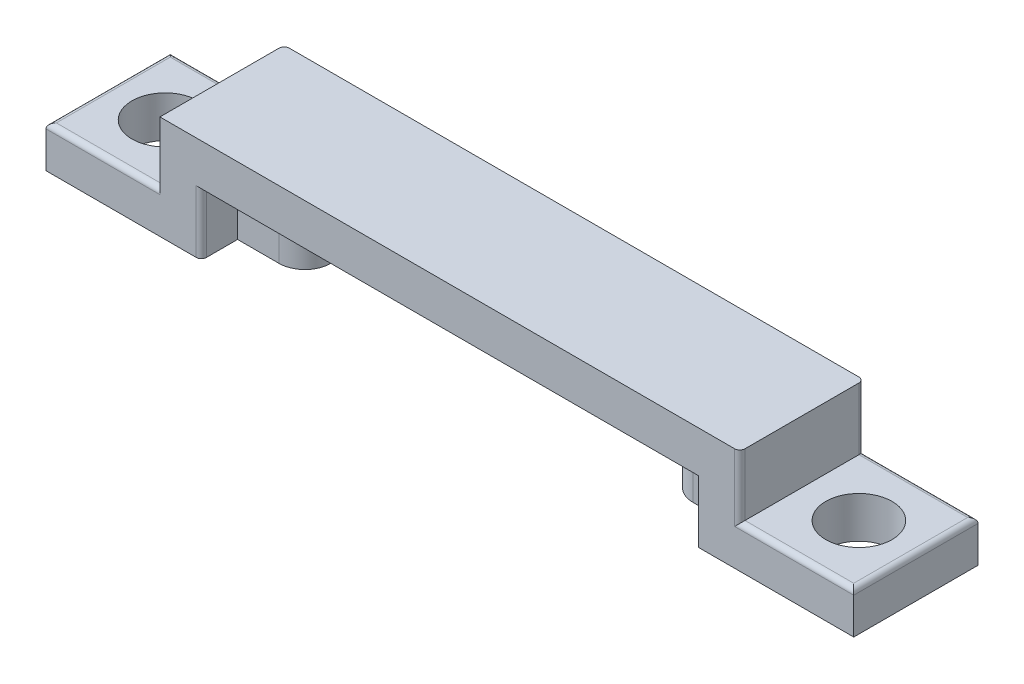
SolidWorks part; units mm, degrees
ref_plane "Ebene vorne" through (0, 0, 0) normal (0, 0, 1) x (1, 0, 0)
ref_plane "Ebene oben" through (0, 0, 0) normal (0, 1, 0) x (1, 0, 0)
ref_plane "Ebene rechts" through (0, 0, 0) normal (1, 0, 0) x (0, 0, -1)
sketch "Skizze1" plane through (0, 0, 0) normal (0, 0, 1) x (1, 0, 0)
  line L0 (0, 0) -> (7.5, 0)
  line L1 (7.5, 0) -> (7.5, 3)
  line L2 (7.5, 3) -> (31.5, 3)
  line L3 (31.5, 3) -> (31.5, 0)
  line L4 (31.5, 0) -> (39, 0)
  line L5 (39, 0) -> (39, 2)
  line L8 (33.5, 5) -> (5.5, 5)
  line L11 (0, 2) -> (0, 0)
  line L12 (33.5, 5) -> (33.5, 2)
  line L13 (31.5, 2) -> (48, 2) construction
  line L14 (33.5, 2) -> (39, 2)
  line L15 (5.5, 5) -> (5.5, 2)
  line L16 (-9, 2) -> (7.5, 2) construction
  line L17 (5.5, 2) -> (0, 2)
  dimension "D1" = 24
  dimension "D2" = 3
  dimension "D3" = 7.5
  dimension "D4" = 7.5
  dimension "D5" = 5
  dimension "D9" = 2
  dimension "D10" = 2
extrude "Aufsatz-Linear austragen1" add sketch "Skizze1" along normal blind 6
sketch "Skizze4" plane through (0, 0, 0) normal (0, -1, 0) x (1, 0, 0)
  line L0 (39, 6) -> (39, 0) construction
  line L1 (31.5, 0) -> (39, 0) construction
  circle A0 centre (36.25, 3) radius 1.6
  dimension "D1" = 3.2
  dimension "D3" = 3
  dimension "D2" = 2.75
extrude "Schnitt-Linear austragen1" cut sketch "Skizze4" against normal blind 3
ref_plane "Ebene1" through (0, 5, 0) normal (0, -1, 0) x (-1, 0, 0)
ref_plane "Ebene2" through (19.5, 0, 0) normal (-1, 0, 0) x (0, 0, 1)
ref_plane "Ebene4" through (0, 0, 3) normal (0, 0, 1) x (1, 0, 0)
sketch "Skizze12" plane through (0, 3, 0) normal (0, -1, 0) x (1, 0, 0)
  line L0 (31.5, 1.75) -> (29.5, 1.75)
  line L1 (31.5, 6) -> (31.5, 0) construction
  line L2 (2.75, 3) -> (-2.75, 3) construction
  line L3 (29.5, 4.25) -> (31.5, 4.25)
  line L4 (31.5, 6) -> (31.5, 0) construction
  line L5 (31.5, 4.25) -> (31.5, 1.75)
  arc A0 (29.5, 1.75) -> (29.5, 4.25) centre (29.5, 3) cw
  dimension "D2" = 1.25
  dimension "D1" = 2
extrude "Aufsatz-Linear austragen2" add sketch "Skizze12" along normal blind 3
mirror "Spiegeln3" about plane through (19.5, 0, 0) normal (-1, 0, 0) of "Aufsatz-Linear austragen2"
mirror "Spiegeln4" about plane through (19.5, 0, 0) normal (-1, 0, 0) of "Schnitt-Linear austragen1"
fillet "Verrundung1" radius 0.25 10 edges at (7.5, 1.5, 6) (33.5, 3.5, 6) (33.5, 3.5, 0) (5.5, 3.5, 0) (2.75, 2, 6) (0, 2, 3) (2.75, 2, 0) (36.25, 2, 0) (39, 2, 3) (36.25, 2, 6)
